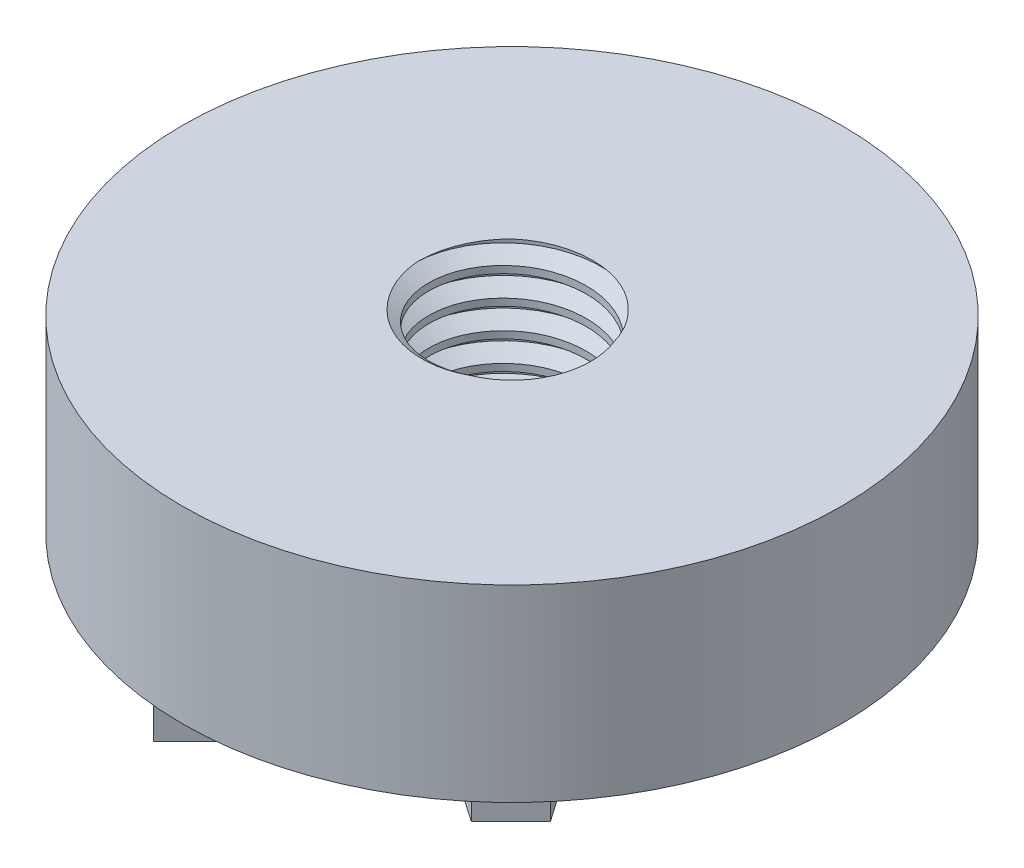
SolidWorks part; units mm, degrees
ref_plane "Alzado" through (0, 0, 0) normal (0, 0, 1) x (1, 0, 0)
ref_plane "Planta" through (0, 0, 0) normal (0, 1, 0) x (1, 0, 0)
ref_plane "Vista lateral" through (0, 0, 0) normal (1, 0, 0) x (0, 0, -1)
sketch "Croquis1" plane through (0, 0, 0) normal (0, 0, 1) x (1, 0, 0)
  line L0 (5, 0) -> (-7.5, 0)
  line L1 (-7.5, 0) -> (-7.5, -5)
  line L3 (-7.5, -5) -> (-7.5, -10)
  line L4 (-7.5, -10) -> (10, -10)
  line L5 (10, -10) -> (10, -8)
  line L6 (5, 0) -> (5, -8)
  line L7 (5, -8) -> (10, -8)
  dimension "D1" = 8
  dimension "D2" = 5
  dimension "D3" = 17.5
  dimension "D4" = 5
  dimension "D5" = 5
revolve "Revolución1" add sketch "Croquis1" angle 360 about L5
thread "Rosca1" pitch 1.5 method extrude profile "Perfil de rosca1" start angle 0, offset 1.5, length 0, pitch 1.5, diameter 10
ref_plane "Plano1" through (5, 1.5, 0) normal (0, 0, 1) x (-1, 0, 0)
sketch "Perfil de rosca1" plane through (5, 1.5, 0) normal (0, 0, 1) x (-1, 0, 0)
  line L0 (0, 0) -> (0, 1.5) construction
  line L11 (0, 0) -> (0, 1.3125)
  line L12 (0, 1.3125) -> (-0.8119, 0.8437)
  line L13 (-0.8119, 0.8437) -> (-0.8119, 0.4687)
  line L15 (-0.8119, 0.4687) -> (0, 0)
  line L17 (-0.8119, 0.6562) -> (0, 0.6562) construction
  point P2 (0, 0)
  dimension "Pitch" = 1.5
  dimension "Profile_Angle" = 60
  dimension "Profile_Land" = 0.375
  dimension "Profile_Height" = 0.8119
sketch "Croquis5" plane through (0, 0, 0) normal (0, 1, 0) x (1, 0, 0)
  circle A0 centre (10, 0) radius 17.5
  circle A1 centre (10, 0) radius 17.5 construction
  point P3 (0, 0)
extrude "Cortar-Extruir1" cut sketch "Croquis5" along normal blind 10
sketch "Croquis4" plane through (0, -10, 0) normal (0, -1, 0) x (1, 0, 0)
  line L0 (-141.5039, -246.875) -> (-141.5039, -34.875) construction
  line L1 (-138.3656, -237.2134) -> (-138.3656, -25.2134) construction
  line L3 (82.7289, 243.5082) -> (424.0622, 243.5082) construction
  line L4 (10.0713, 2.3632) -> (16.432, 8.724)
  line L5 (16.432, 8.724) -> (16.9315, 10.1092)
  line L6 (16.9315, 10.1092) -> (20.1542, 12.3143)
  line L7 (20.1542, 12.3143) -> (22.2556, 10.2129)
  line L8 (22.2556, 10.2129) -> (20.0412, 7.0183)
  line L9 (20.0412, 7.0183) -> (18.5994, 6.5566)
  line L10 (18.5994, 6.5566) -> (12.2387, 0.1959)
  line L11 (12.2387, 0.1959) -> (13.7747, -1.3401)
  line L12 (13.7747, -1.3401) -> (12.1067, -3.0081)
  line L13 (12.1067, -3.0081) -> (10.4328, -3.5442)
  line L14 (10.4328, -3.5442) -> (9.8442, -5.1766)
  line L15 (9.8442, -5.1766) -> (3.2961, -11.7248)
  line L16 (10.0713, 2.3632) -> (8.639, 3.7956)
  line L17 (8.639, 3.7956) -> (6.971, 2.1276)
  line L18 (6.971, 2.1276) -> (6.4208, 0.6016)
  line L19 (6.4208, 0.6016) -> (4.8189, -0.1513)
  line L20 (4.8189, -0.1513) -> (-1.7927, -6.636)
  line L21 (0.1391, -7.9459) -> (5.6895, -2.3955)
  line L22 (1.8353, -9.9436) -> (7.6212, -4.1577)
  line L23 (16.101, 9.055) -> (7.812, 17.3441) construction
  line L24 (15.8043, 9.3518) -> (14.8497, 8.3972)
  line L25 (14.8497, 8.3972) -> (14.1784, 9.0685)
  line L26 (14.1784, 9.0685) -> (10.0235, 4.9137)
  line L27 (10.0235, 4.9137) -> (10.6949, 4.2423)
  line L28 (10.6949, 4.2423) -> (9.7224, 3.2699)
  line L29 (9.7224, 3.2699) -> (1.9865, 11.0058)
  line L30 (1.9865, 11.0058) -> (2.9411, 11.9604)
  line L31 (2.9411, 11.9604) -> (3.5699, 11.3315)
  line L32 (3.5699, 11.3315) -> (7.812, 15.5736)
  line L33 (7.812, 15.5736) -> (7.1832, 16.2024)
  line L34 (7.1832, 16.2024) -> (8.0684, 17.0877)
  line L35 (8.0684, 17.0877) -> (15.8043, 9.3518)
  line L36 (8.8319, 6.1442) -> (12.97, 10.2823)
  line L37 (12.97, 10.2823) -> (11.575, 11.6773)
  line L38 (11.575, 11.6773) -> (7.4369, 7.5392)
  line L39 (7.4369, 7.5392) -> (8.8319, 6.1442)
  line L40 (6.2521, 8.724) -> (4.8189, 10.1572)
  line L41 (4.8189, 10.1572) -> (8.9624, 14.3007)
  line L42 (8.9624, 14.3007) -> (10.3956, 12.8675)
  line L43 (10.3956, 12.8675) -> (6.2521, 8.724)
  arc A1 (3.2961, -11.7248) -> (-1.7927, -6.636) centre (1.0191, -8.913) cw
  arc A2 (1.8353, -9.9436) -> (0.1391, -7.9459) centre (1.1956, -8.7678) cw
  arc A3 (7.6212, -4.1577) -> (5.6895, -2.3955) centre (6.5247, -3.4199) ccw
  point P53 (7.812, 15.5736)
  point P54 (10.0235, 4.9137)
  dimension "D1" = 1.35
  dimension "D2" = 1.35
extrude "Saliente-Extruir1" add sketch "Croquis4" along normal blind 2
